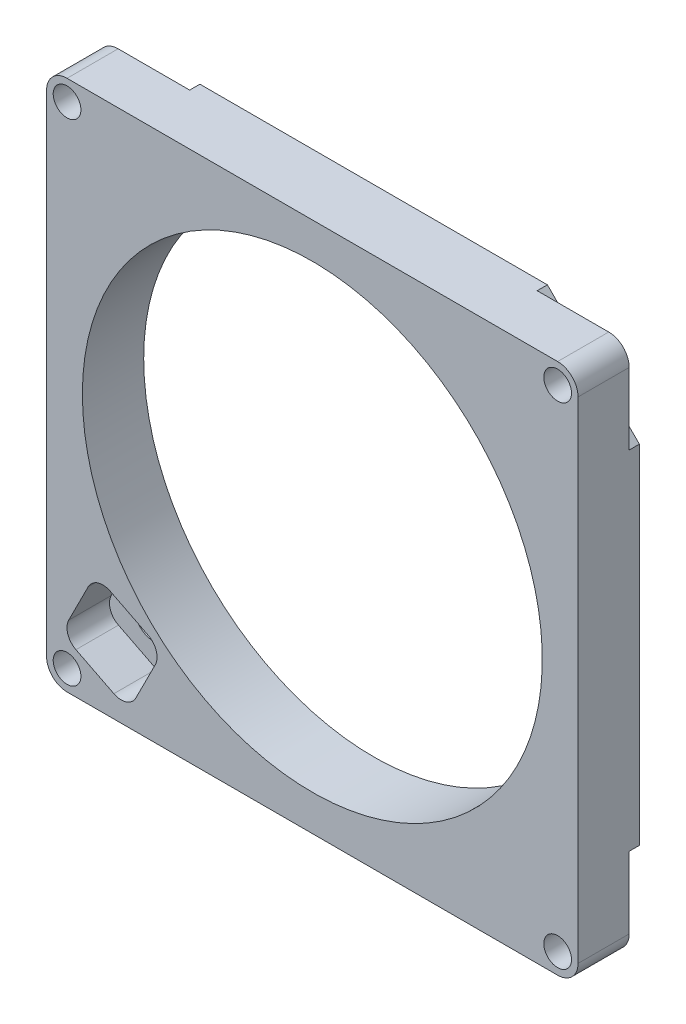
SolidWorks part; units mm, degrees
material "PET"
ref_plane "Front Plane" through (0, 0, 0) normal (0, 0, 1) x (1, 0, 0)
ref_plane "Top Plane" through (0, 0, 0) normal (0, 1, 0) x (1, 0, 0)
ref_plane "Right Plane" through (0, 0, 0) normal (1, 0, 0) x (0, 0, -1)
sketch "Sketch1" plane through (0, 0, 0) normal (0, 0, 1) x (1, 0, 0)
  line L8 (-213.995, 2363.8407) -> (-213.995, 2440.0407)
  line L9 (-217.17, 2443.2157) -> (-293.37, 2443.2157)
  line L10 (-296.545, 2440.0407) -> (-296.545, 2363.8407)
  line L11 (-293.37, 2360.6657) -> (-217.17, 2360.6657)
  arc A8 (-217.17, 2360.6657) -> (-213.995, 2363.8407) centre (-217.17, 2363.8407) ccw
  arc A9 (-213.995, 2440.0407) -> (-217.17, 2443.2157) centre (-217.17, 2440.0407) ccw
  arc A10 (-293.37, 2443.2157) -> (-296.545, 2440.0407) centre (-293.37, 2440.0407) ccw
  arc A11 (-296.545, 2363.8407) -> (-293.37, 2360.6657) centre (-293.37, 2363.8407) ccw
extrude "Boss-Extrude1" add sketch "Sketch1" against normal up to surface (7.9375 mm away)
sketch "Sketch2" plane through (0, 0, -7.9375) normal (0, 0, -1) x (-1, 0, 0)
  line L16 (282.2575, 2360.6657) -> (296.545, 2374.9532)
  line L17 (296.545, 2374.9532) -> (296.545, 2428.9282)
  line L18 (296.545, 2428.9282) -> (282.2575, 2443.2157)
  line L19 (282.2575, 2443.2157) -> (228.2825, 2443.2157)
  line L20 (228.2825, 2443.2157) -> (213.995, 2428.9282)
  line L21 (213.995, 2428.9282) -> (213.995, 2374.9532)
  line L22 (213.995, 2374.9532) -> (228.2825, 2360.6657)
  line L23 (228.2825, 2360.6657) -> (282.2575, 2360.6657)
  circle A1 centre (255.27, 2401.9407) radius 35.7188
extrude "Boss-Extrude2" add sketch "Sketch2" along normal blind 1.5875
sketch "Sketch3" plane through (0, 0, -7.9375) normal (0, 0, -1) x (-1, 0, 0)
  circle A1 centre (255.27, 2401.9407) radius 35.7188
  circle A2 centre (255.27, 2401.9407) radius 35.7188
  dimension "D1" = 0
extrude "Cut-Extrude1" cut sketch "Sketch3" against normal through all and the other way through all
hole_wizard "#6 Clearance Hole1" positions "Sketch5" profile "Sketch4" hole size "#6" standard "ANSI Inch" end condition through all
sketch "Sketch5" plane through (0, 0, -7.9375) normal (0, 0, -1) x (-1, 0, 0)
  point P0 (217.17, 2440.0407)
  point P2 (293.37, 2440.0407)
  point P4 (293.37, 2363.8407)
  point P6 (217.17, 2363.8407)
sketch "Sketch4" plane through (-217.17, 2440.0407, -7.9375) normal (1, 0, 0) x (0, 1, 0)
  line L0 (0, 0) -> (0, 7.9375)
  line L1 (0, 7.9375) -> (2.1526, 7.9375)
  line L2 (2.1526, 7.9375) -> (2.1526, 0)
  line L5 (2.1526, 0) -> (0, 0)
  line L11 (0, -6.35) -> (0, 107.95) construction
  dimension "Thru Hole Dia." = 4.3053
  dimension "Thru Hole Depth" = 7.9375
sketch "Sketch6" plane through (0, 0, 0) normal (0, 0, 1) x (1, 0, 0)
  line L0 (-286.0983, 2364.0731) -> (-291.989, 2367.0475)
  line L1 (-282.6861, 2365.1956) -> (-279.6585, 2371.1918)
  line L2 (-293.1115, 2370.4597) -> (-290.0839, 2376.4558)
  line L3 (-280.781, 2374.604) -> (-286.6717, 2377.5783)
  line L4 (-283.831, 2362.9283) -> (-288.939, 2378.7232) construction
  line L5 (-294.2563, 2368.1923) -> (-278.5137, 2373.4591) construction
  line L6 (-286.385, 2370.8257) -> (-291.5977, 2373.4577) construction
  arc A0 (-279.6585, 2371.1918) -> (-280.781, 2374.604) centre (-281.9259, 2372.3366) ccw
  arc A1 (-282.6861, 2365.1956) -> (-286.0983, 2364.0731) centre (-284.9535, 2366.3405) cw
  arc A2 (-290.0839, 2376.4558) -> (-286.6717, 2377.5783) centre (-287.8165, 2375.311) cw
  arc A3 (-291.989, 2367.0475) -> (-293.1115, 2370.4597) centre (-290.8441, 2369.3148) cw
  point P0 (-291.5977, 2373.4577)
  point P2 (-286.385, 2370.8257)
  dimension "D1" = 2.54
extrude "Cut-Extrude2" cut sketch "Sketch6" against normal offset from surface (6.604 mm away) 2.921 up to face at (-255.27, 2401.9407, -9.525)
hole_wizard "F (0.257) Diameter Hole1" positions "Sketch8" profile "Sketch7" hole size "F" standard "ANSI Inch" end condition through all
sketch "Sketch8" plane through (0, 0, -9.525) normal (0, 0, -1) x (-1, 0, 0)
  point P0 (286.385, 2370.8257)
sketch "Sketch7" plane through (-286.385, 2370.8257, -9.525) normal (1, 0, 0) x (0, 1, 0)
  line L0 (0, 0) -> (0, 9.525)
  line L1 (0, 9.525) -> (3.2639, 9.525)
  line L2 (3.2639, 9.525) -> (3.2639, 0)
  line L5 (3.2639, 0) -> (0, 0)
  line L11 (0, -6.35) -> (0, 107.95) construction
  dimension "Thru Hole Dia." = 6.5278
  dimension "Thru Hole Depth" = 9.525
hole_wizard "#51 (0.067) Diameter Hole1" positions "Sketch9" profile "Sketch10" hole size "#51" standard "ANSI Inch" end condition through all
sketch "Sketch9" plane through (0, 0, -9.525) normal (0, 0, -1) x (-1, 0, 0)
  point P0 (290.6199, 2373.0045)
sketch "Sketch10" plane through (-290.6199, 2373.0045, -9.525) normal (1, 0, 0) x (0, 1, 0)
  line L0 (0, 0) -> (0, 9.525)
  line L1 (0, 9.525) -> (0.8509, 9.525)
  line L2 (0.8509, 9.525) -> (0.8509, 0)
  line L5 (0.8509, 0) -> (0, 0)
  line L11 (0, -6.35) -> (0, 107.95) construction
  dimension "Thru Hole Dia." = 1.7018
  dimension "Thru Hole Depth" = 9.525
